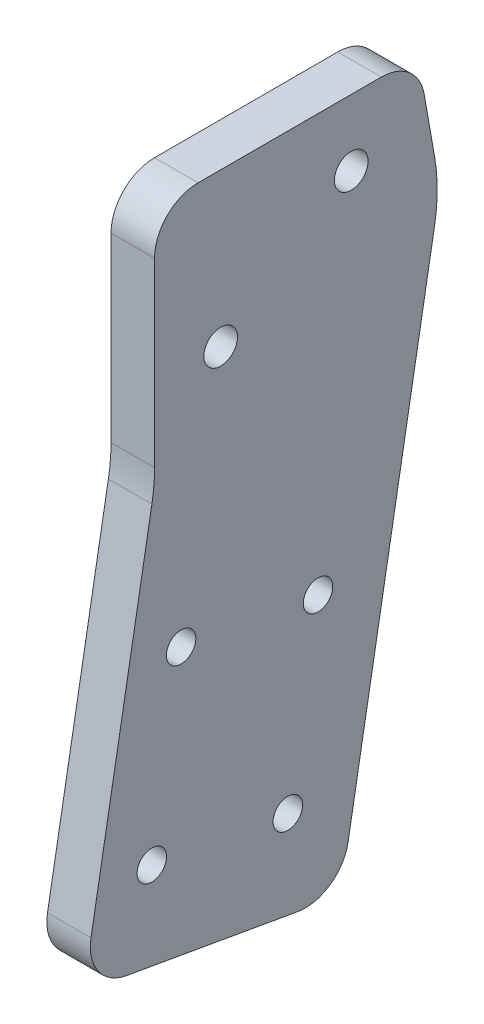
SolidWorks part; units mm, degrees
material "6061-T6 (SS)"
ref_plane "Front Plane" through (0, 0, 0) normal (0, 0, 1) x (1, 0, 0)
ref_plane "Top Plane" through (0, 0, 0) normal (0, 1, 0) x (1, 0, 0)
ref_plane "Right Plane" through (0, 0, 0) normal (1, 0, 0) x (0, 0, -1)
sketch "Sketch1" plane through (5.0358, 0, 0) normal (-1, 0, 0) x (0, 0, 1)
  line L0 (-147.7756, 230.0705) -> (-162.2698, 312.271)
  line L1 (-162.2698, 312.271) -> (-159.0451, 330.559)
  line L2 (-159.0451, 330.559) -> (-120.6268, 330.559)
  line L3 (-120.6268, 330.559) -> (-120.6268, 295.5112)
  line L4 (-147.7756, 230.0705) -> (-110.2544, 236.6865)
  line L5 (-139.5479, 183.4086) -> (-158.6812, 291.9191) construction
  line L6 (-110.2544, 236.6865) -> (-120.6268, 295.5112)
  line L7 (-72.8031, 24.2892) -> (-117.5036, 277.7986) construction
  line L8 (-126.9495, 330.559) -> (-152.9373, 330.559) construction
  circle A0 centre (-140.0751, 244.3242) radius 2.1527 construction
  point P15 (-159.3146, 295.5112)
  point P16 (-159.3146, 295.5112)
  point P17 (-159.3146, 295.5112)
  point P18 (-162.0313, 311.9253)
  point P19 (-161.8387, 311.6368)
  point P20 (-162.3936, 312.3764)
  dimension "D3" = 12.7
  dimension "D1" = 0
  dimension "D2" = 0
  dimension "D4" = 100
  dimension "D5" = 18.288
extrude "Boss-Extrude1" add sketch "Sketch1" along normal blind 6.35
fillet "Fillet1" radius 25.4 2 edges at (1.8608, 295.5112, -120.6268) (1.8608, 312.271, -162.2698)
hole_wizard "CSK for #6 Flat Head Machine Screw (100)1" positions "Sketch3" profile "Sketch2" countersink size "#6" standard "ANSI Inch" end condition through all
sketch "Sketch3" plane through (-1.3142, 0, 0) normal (-1, 0, 0) x (0, 0, 1)
  point P0 (-124.5041, 273.1394)
  point P3 (-144.4852, 269.7242)
  point P6 (-140.0751, 244.3242)
  point P9 (-120.2274, 247.7166)
sketch "Sketch2" plane through (-1.3142, 273.1394, -124.5041) normal (0, 1, 0) x (0, 0, 1)
  line L0 (0, 0) -> (0, 6.35)
  line L1 (0, 6.35) -> (2.1526, 6.35)
  line L2 (2.1526, 6.35) -> (2.1526, 1.1669)
  line L3 (2.1526, 1.1669) -> (3.5433, 0)
  line L5 (3.5433, 0) -> (0, 0)
  line L6 (-2.1526, 1.1669) -> (-3.5433, 0) construction
  line L11 (0, -6.35) -> (0, 107.95) construction
  dimension "Thru Hole Dia." = 4.3053
  dimension "Thru Hole Depth" = 6.35
  dimension "Near C'Sink Dia." = 7.0866
  dimension "Near C'Sink Angle" = 100
hole_wizard "CSK for #8 Flat Head Machine Screw (100)1" positions "Sketch4" profile "Sketch5" countersink size "#8" standard "ANSI Inch" end condition through all
sketch "Sketch4" plane through (-1.3142, 0, 0) normal (-1, 0, 0) x (0, 0, 1)
  point P0 (-149.3288, 320.907)
  point P2 (-130.2788, 308.207)
sketch "Sketch5" plane through (-1.3142, 320.907, -149.3288) normal (0, 1, 0) x (0, 0, 1)
  line L0 (0, 0) -> (0, 6.35)
  line L1 (0, 6.35) -> (2.4574, 6.35)
  line L2 (2.4574, 6.35) -> (2.4574, 1.4759)
  line L3 (2.4574, 1.4759) -> (4.2164, 0)
  line L5 (4.2164, 0) -> (0, 0)
  line L6 (-2.4574, 1.4759) -> (-4.2164, 0) construction
  line L11 (0, -6.35) -> (0, 107.95) construction
  dimension "Thru Hole Dia." = 4.9149
  dimension "Thru Hole Depth" = 6.35
  dimension "Near C'Sink Dia." = 8.4328
  dimension "Near C'Sink Angle" = 100
chamfer "Chamfer1" [suppressed] distance 2.54 angle 45
chamfer "Chamfer2" [suppressed] distance 6.35 angle 45
fillet "Fillet2" radius 6.35 4 edges at (1.8608, 330.559, -120.6268) (1.8608, 330.559, -159.0451) (1.8608, 236.6865, -110.2544) (1.8608, 230.0705, -147.7756)
